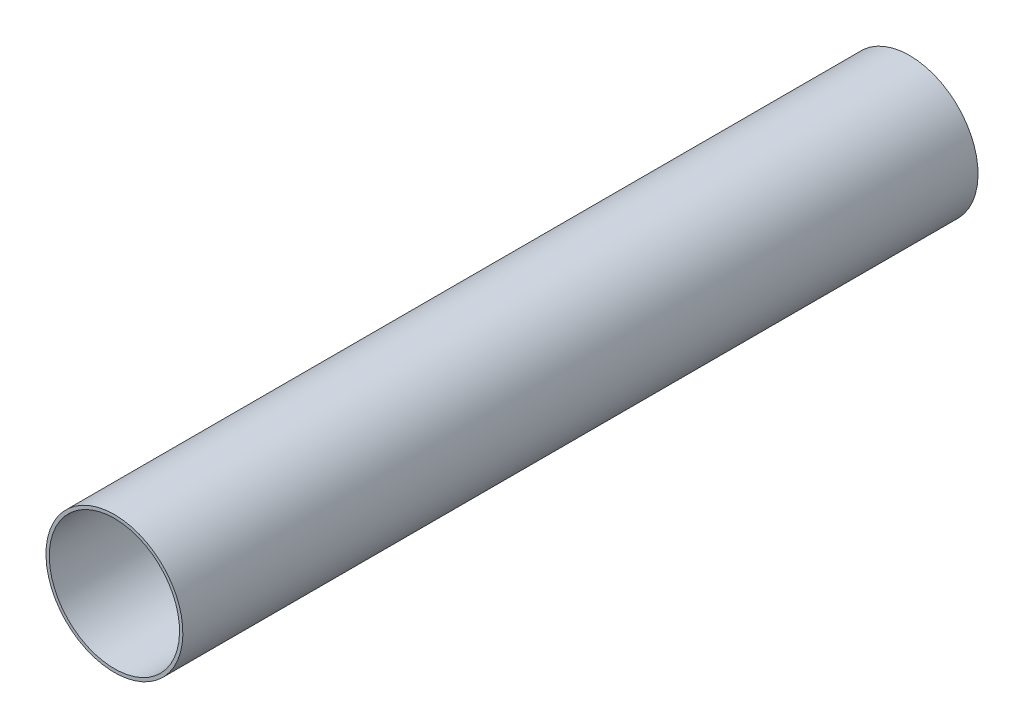
SolidWorks part; units mm, degrees
ref_plane "Plan de face" through (0, 0, 0) normal (0, 0, 1) x (1, 0, 0)
ref_plane "Plan de dessus" through (0, 0, 0) normal (0, 1, 0) x (1, 0, 0)
ref_plane "Plan de droite" through (0, 0, 0) normal (1, 0, 0) x (0, 0, -1)
sketch "Esquisse2" plane through (0, 0, 0) normal (1, 0, 0) x (0, 0, -1)
  line L0 (-10, 51.649) -> (-10, 49.149)
  line L2 (-10, 49.149) -> (-610, 49.149)
  line L12 (0, 49.149) -> (-388.9502, 49.149) construction
  line L19 (-610, 49.149) -> (-610, 51.649)
  line L20 (-610, 51.649) -> (-10, 51.649)
  line L24 (0, 0) -> (-694.9162, 0) construction
  dimension "D1" = 10
  dimension "D2" = 600
  dimension "D3" = 2.5
revolve "Révolution1" add sketch "Esquisse2" angle 360 about L24
